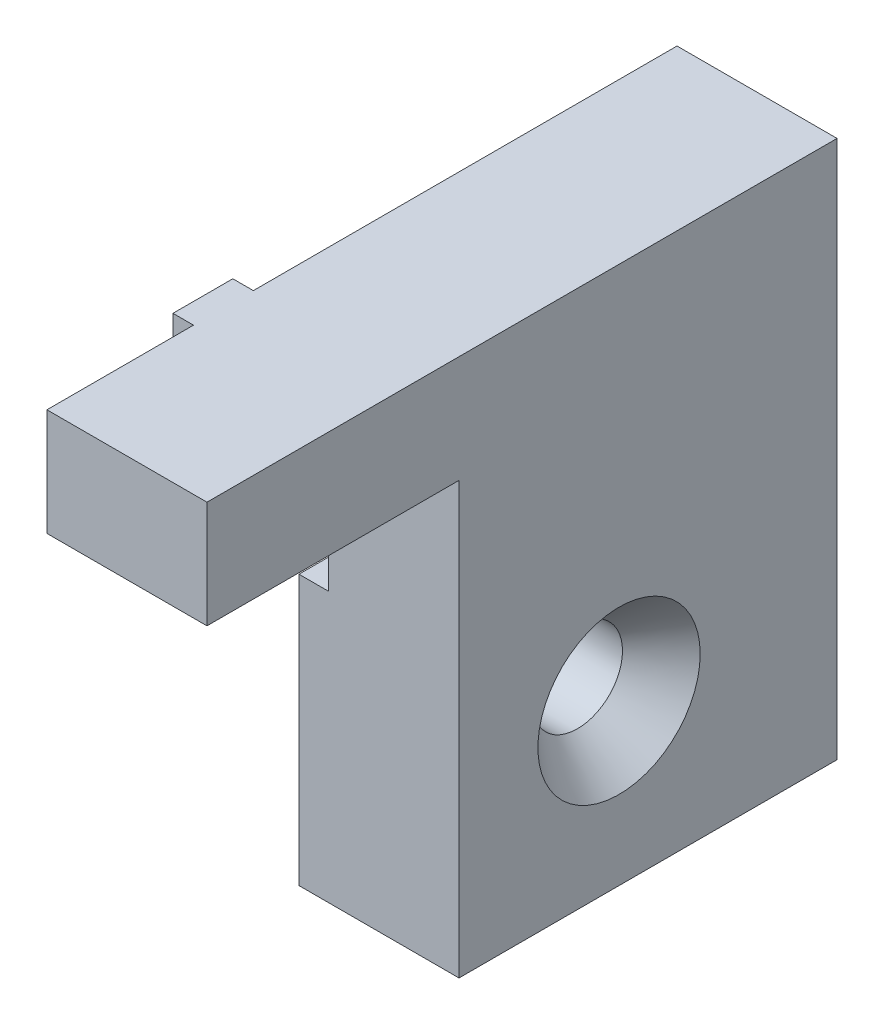
SolidWorks part; units mm, degrees
ref_plane "Front Plane" through (0, 0, 0) normal (0, 0, 1) x (1, 0, 0)
ref_plane "Top Plane" through (0, 0, 0) normal (0, 1, 0) x (1, 0, 0)
ref_plane "Right Plane" through (0, 0, 0) normal (1, 0, 0) x (0, 0, -1)
sketch "Sketch1" plane through (0, 0, 0) normal (1, 0, 0) x (0, 0, -1)
  line L0 (30, -34.2) -> (0, -34.2)
  line L1 (30, -34.2) -> (30, 8.5)
  line L2 (30, 8.5) -> (0, 8.5)
  line L3 (0, -34.2) -> (0, 8.5)
  line L4 (-20, 8.5) -> (0, 8.5)
  line L5 (-20, 8.5) -> (-20, 0)
  line L6 (-20, 0) -> (0, 0)
  line L7 (0, 8.5) -> (0, 0)
  circle A0 centre (12.7, -21.5) radius 3.175
  dimension "D1" = 6.35
  dimension "D2" = 12.7
  dimension "D3" = 12.7
  dimension "D4" = 30
  dimension "D5" = 20
  dimension "D6" = 8.5
  dimension "D7" = 42.7
extrude "Boss-Extrude1" add sketch "Sketch1" along normal blind 12.7 contours L3 L0 L1 L2 A0 | L5 L6 L3 L4 region at (0, -12.6307, -15.0583) region at (0, 4.25, 10)
hole_wizard "CSK for 1/4 Flat Head Machine Screw1" positions "3DSketch1" profile "Sketch2" countersink size "1/4" standard "ANSI Inch" end condition through all
sketch3d "3DSketch1"
  line L0 (12.7, -21.5, -12.7) -> (0, -21.5, -12.7) construction
  point P0 (12.7, -21.5, -12.7)
  point P3 (12.7, -21.5, -12.7)
sketch "Sketch2" plane through (12.7, -21.5, -12.7) normal (0, 1, 0) x (0, 0, -1)
  line L0 (0, 0) -> (0, 12.7)
  line L1 (0, 12.7) -> (3.5712, 12.7)
  line L2 (3.5712, 12.7) -> (3.5712, 3.2989)
  line L3 (3.5712, 3.2989) -> (6.4389, 0)
  line L5 (6.4389, 0) -> (0, 0)
  line L6 (-3.5712, 3.2989) -> (-6.4389, 0) construction
  line L11 (0, -6.35) -> (0, 107.95) construction
  dimension "Thru Hole Dia." = 7.1425
  dimension "Thru Hole Depth" = 12.7
  dimension "Near C'Sink Dia." = 12.8778
  dimension "Near C'Sink Angle" = 82
sketch "Sketch3" plane through (0, 0, 0) normal (-1, 0, 0) x (0, 0, 1)
  line L1 (0, 0) -> (-8, 0)
  line L2 (0, 0) -> (0, -12.8)
  line L3 (0, -12.8) -> (-8, -12.8)
  line L4 (-8, 0) -> (-8, -12.8)
  dimension "D1" = 8
  dimension "D2" = 12.8
extrude "Cut-Extrude1" cut sketch "Sketch3" against normal blind 2.35
sketch "Sketch4" plane through (0, 0, 0) normal (-1, 0, 0) x (0, 0, 1)
  line L0 (-30, 8.5) -> (20, 8.5) construction
  line L1 (8.37, 8.5) -> (3.62, 8.5)
  line L2 (8.37, 8.5) -> (8.37, 0)
  line L3 (8.37, 0) -> (3.62, 0)
  line L4 (3.62, 8.5) -> (3.62, 0)
  line L5 (20, 0) -> (-8, 0) construction
  line L6 (20, 8.5) -> (20, 0) construction
  dimension "D1" = 11.63
  dimension "D2" = 4.75
extrude "Boss-Extrude2" add sketch "Sketch4" along normal blind 1.63
